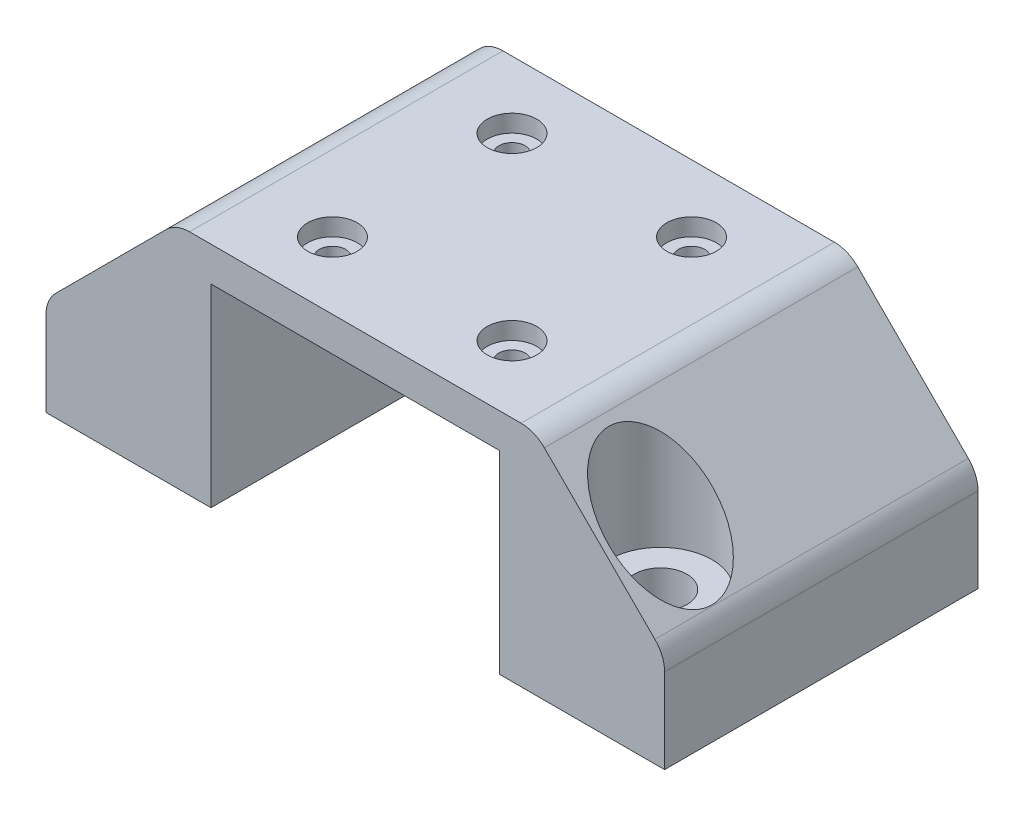
SolidWorks part; units mm, degrees
ref_plane "Front Plane" through (0, 0, 0) normal (0, 0, 1) x (1, 0, 0)
ref_plane "Top Plane" through (0, 0, 0) normal (0, 1, 0) x (1, 0, 0)
ref_plane "Right Plane" through (0, 0, 0) normal (1, 0, 0) x (0, 0, -1)
sketch "Sketch1" plane through (0, 0, 0) normal (0, 0, 1) x (1, 0, 0)
  line L0 (0, -12.67) -> (0, 30.502) construction
  line L1 (-11.1125, 0) -> (-11.1125, 14.9225)
  line L2 (-11.1125, 0) -> (-23.8125, 0)
  line L3 (-11.1125, 14.9225) -> (11.1125, 14.9225)
  line L4 (-23.8125, 17.5746) -> (23.8125, 17.5746)
  line L5 (-23.8125, 0) -> (-23.8125, 17.5746)
  line L6 (11.1125, 0) -> (23.8125, 0)
  line L7 (23.8125, 0) -> (23.8125, 17.5746)
  line L8 (11.1125, 0) -> (11.1125, 14.9225)
  point P9 (0, 17.5746)
  point P13 (0, 14.9225)
  dimension "D1" = 12.7
  dimension "D2" = 11.1125
  dimension "D3" = 14.9225
  dimension "D4" = 17.5746
extrude "Boss-Extrude1" add sketch "Sketch1" along normal blind 24.13
chamfer "Chamfer1" distance 10 angle 45 2 edges at (23.8125, 17.5746, 12.065) (-23.8125, 17.5746, 12.065)
fillet "Fillet1" radius 2.54 2 edges at (13.8125, 17.5746, 12.065) (-13.8125, 17.5746, 12.065)
fillet "Fillet2" radius 2.54 2 edges at (23.8125, 7.5746, 12.065) (-23.8125, 7.5746, 12.065)
sketch "Sketch2" plane through (0, 0, 0) normal (0, -1, 0) x (1, 0, 0)
  line L0 (0, -12.2519) -> (0, 31.6273) construction
  line L1 (-35.4754, 12.065) -> (35.4754, 12.065) construction
  line L2 (-11.1125, 0) -> (11.1125, 0) construction
  circle A0 centre (-19.05, 19.685) radius 2.032
  circle A1 centre (19.05, 19.685) radius 2.032
  dimension "D1" = 4.064
  dimension "D2" = 7.62
  dimension "D3" = 12.065
  dimension "D4" = 19.05
extrude "Cut-Extrude1" cut sketch "Sketch2" against normal blind 10.16
sketch "Sketch3" plane through (0, 17.5746, 0) normal (0, 1, 0) x (1, 0, 0)
  line L0 (0, 9.1955) -> (0, -28.8887) construction
  line L1 (-14.5564, -12.065) -> (14.5564, -12.065) construction
  line L2 (-14.5564, -24.13) -> (-14.5564, 0) construction
  line L3 (14.5564, 0) -> (14.5564, -24.13) construction
  circle A0 centre (-6.9113, -5.1537) radius 1.016
  circle A1 centre (6.9113, -5.1537) radius 1.016
  circle A2 centre (6.9113, -18.9763) radius 1.016
  circle A3 centre (-6.9113, -18.9763) radius 1.016
  dimension "D3" = 2.032
  dimension "D1" = 6.9113
  dimension "D2" = 6.9113
extrude "Cut-Extrude2" cut sketch "Sketch3" against normal through all
sketch "Sketch4" plane through (0, 17.5746, 0) normal (0, 1, 0) x (1, 0, 0)
  line L0 (0, 10.8653) -> (0, -31.1365) construction
  line L1 (-14.5564, -12.065) -> (14.5564, -12.065) construction
  line L2 (-14.5564, -24.13) -> (-14.5564, 0) construction
  line L3 (14.5564, 0) -> (14.5564, -24.13) construction
  circle A0 centre (-6.9113, -5.1537) radius 1.905
  circle A1 centre (6.9113, -5.1537) radius 1.905
  circle A2 centre (6.9113, -18.9763) radius 1.905
  circle A3 centre (-6.9113, -18.9763) radius 1.905
  dimension "D1" = 3.81
extrude "Cut-Extrude3" cut sketch "Sketch4" against normal blind 1.3335
sketch "Sketch5" plane through (0, 0, 0) normal (0, -1, 0) x (1, 0, 0)
  line L0 (0, 26.4248) -> (0, -11.0183) construction
  line L1 (-23.8125, 12.065) -> (23.8125, 12.065) construction
  line L2 (-23.8125, 24.13) -> (-23.8125, 0) construction
  line L3 (23.8125, 24.13) -> (23.8125, 0) construction
  circle A0 centre (-19.05, 4.445) radius 2.032
  circle A2 centre (19.05, 4.445) radius 2.032
  dimension "D3" = 4.064
  dimension "D1" = 7.62
  dimension "D2" = 19.05
extrude "Cut-Extrude4" cut sketch "Sketch5" against normal blind 8.89
sketch "Sketch7" plane through (0, 17.5746, 0) normal (0, 1, 0) x (1, 0, 0)
  line L0 (0, 10.3263) -> (0, -35.1994) construction
  line L1 (-23.8125, -12.065) -> (23.8125, -12.065) construction
  line L2 (-23.8125, -24.13) -> (-23.8125, 0) construction
  line L3 (23.8125, 0) -> (23.8125, -24.13) construction
  circle A2 centre (19.05, -19.685) radius 3.9688
  circle A3 centre (-19.05, -19.685) radius 3.9688
extrude "Cut-Extrude5" cut sketch "Sketch7" against normal blind 10.16
